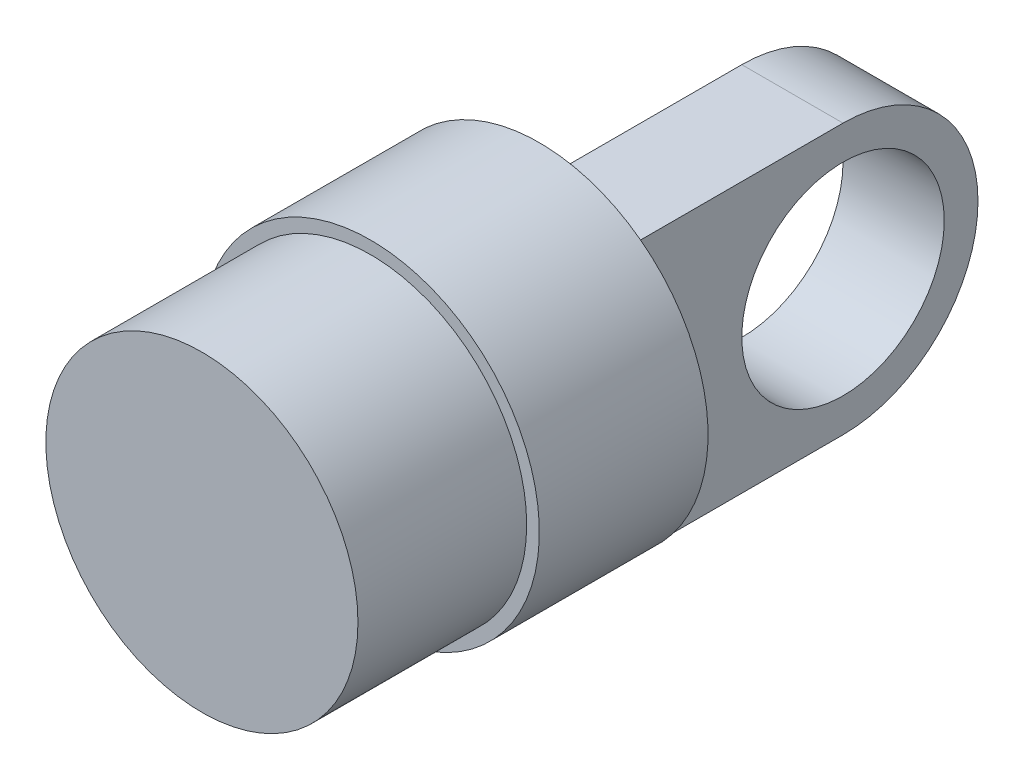
SolidWorks part; units mm, degrees
material "Stainless Steel (ferritic)"
ref_plane "Front Plane" through (0, 0, 0) normal (0, 0, 1) x (1, 0, 0)
ref_plane "Top Plane" through (0, 0, 0) normal (0, 1, 0) x (1, 0, 0)
ref_plane "Right Plane" through (0, 0, 0) normal (1, 0, 0) x (0, 0, -1)
sketch "Sketch1" plane through (0, 0, 0) normal (0, 0, 1) x (1, 0, 0)
  circle A0 centre (0, 0) radius 9.25
  dimension "D1" = 18.5
extrude "Boss-Extrude1" add sketch "Sketch1" along normal blind 10 contours A0
sketch "Sketch2" plane through (0, 0, 0) normal (0, 0, -1) x (-1, 0, 0)
  circle A0 centre (0, 0) radius 10
  dimension "D1" = 20
extrude "Boss-Extrude2" add sketch "Sketch2" along normal blind 10
sketch "Sketch3" plane through (0, 0, -10) normal (0, 0, -1) x (-1, 0, 0)
  line L0 (0, -8) -> (0, 8) construction
  line L1 (-6, -8) -> (6, -8)
  line L2 (-6, -8) -> (-6, 8)
  line L3 (-6, 8) -> (6, 8)
  line L4 (6, -8) -> (6, 8)
  line L5 (-6, 0) -> (6, 0) construction
  point P8 (0, 0)
  dimension "D1" = 12
  dimension "D2" = 16
extrude "Boss-Extrude3" add sketch "Sketch3" along normal blind 20 contours L3 L4 L1 L2
sketch "Sketch4" plane through (6, 0, 0) normal (1, 0, 0) x (0, 0, -1)
  line L0 (22, 8) -> (22, -8) construction
  line L1 (30, 8) -> (10, 8) construction
  line L2 (30, -8) -> (30, 8) construction
  arc A0 (22, 8) -> (22, -8) centre (22, 0) cw
  circle A1 centre (22, 0) radius 6
  line M3 (10, -8) -> (30, -8)
  line M4 (30, -8) -> (30, 8)
  line M5 (30, 8) -> (10, 8)
  dimension "D1" = 12
extrude "Cut-Extrude1" cut sketch "Sketch4" against normal blind 30 and the other way through all contours A0 M5 M4 | A0 M4 M3 region at (6, 6.2131, -28.2131) region at (6, -6.2131, -28.2131)
extrude "Cut-Extrude2" cut sketch "Sketch4<3>" against normal through all contours L0 A1 | A1 L0 region at (6, 0, -24.5465) region at (6, 0, -19.4535)
sketch "Sketch4<3>" plane through (6, 0, 0) normal (1, 0, 0) x (0, 0, -1) same geometry as "Sketch4"
sketch "Sketch5" plane through (0, 8, 0) normal (0, 1, 0) x (1, 0, 0)
  line L0 (6, 10) -> (-6, 10) construction
  line L1 (-6, 30) -> (0, 30)
  line L2 (-6, 30) -> (-6, 10)
  line L3 (-6, 10) -> (0, 10)
  line L4 (0, 30) -> (0, 10)
extrude "Cut-Extrude3" cut sketch "Sketch5" against normal through all
ref_axis "HerrajeBase" through (0, 0, 10) along (0, 0, -1)
ref_axis "HerrajeEnganche" through (0, 0, -22) along (1, 0, 0)
